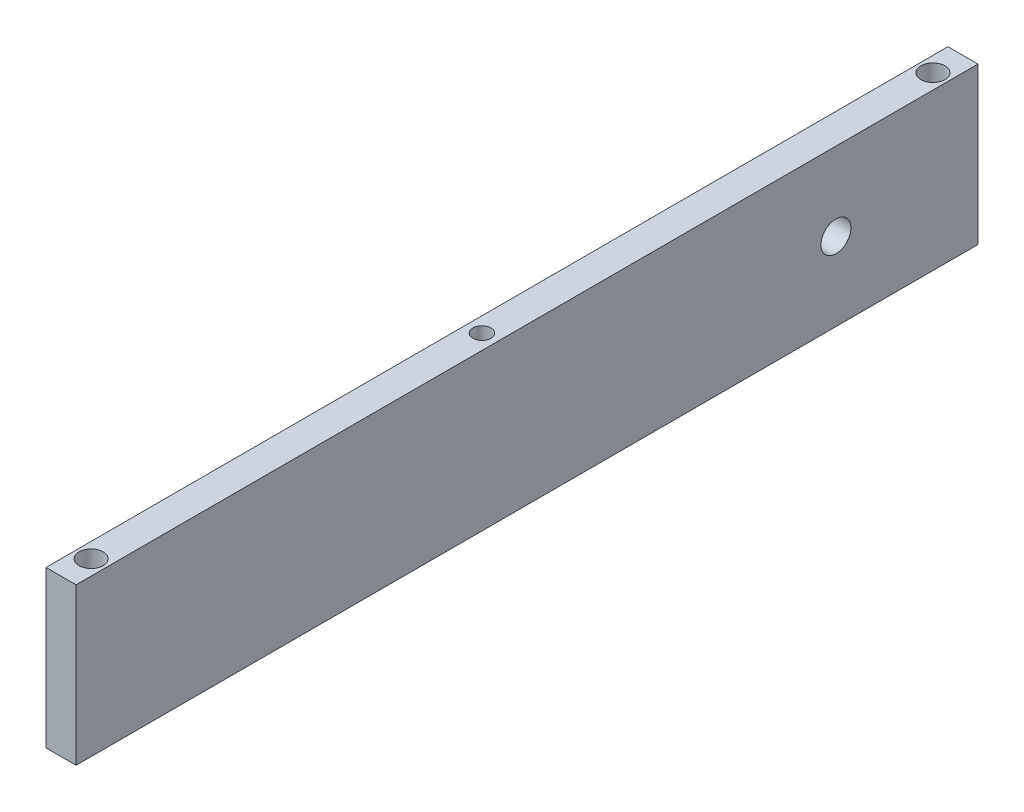
SolidWorks part; units mm, degrees
other "Markup1"
sketch "Sketch6" plane through (0, 0, 0) normal (0.7258, -0.6292, 0.2781) x (-0.261, -0.6259, -0.735)
ref_plane "Front Plane" through (0, 0, 0) normal (0, 0, 1) x (1, 0, 0)
ref_plane "Top Plane" through (0, 0, 0) normal (0, 1, 0) x (1, 0, 0)
ref_plane "Right Plane" through (0, 0, 0) normal (1, 0, 0) x (0, 0, -1)
sketch "Sketch1" plane through (0, 0, 0) normal (0, 0, 1) x (1, 0, 0)
  line L1 (-6.35, 0) -> (-6.35, 33.02)
  line L2 (-6.35, 33.02) -> (0, 33.02)
  line L3 (0, 33.02) -> (0, 0)
  line L6 (-6.35, 0) -> (0, 0)
  dimension "D3" = 6.35
  dimension "D4" = 33.02
extrude "Boss-Extrude1" add sketch "Sketch1" against normal blind 190.5
sketch "Sketch2" plane through (-6.35, 0, 0) normal (-1, 0, 0) x (0, 0, 1)
  line L0 (-190.5, 33.02) -> (-190.5, 0) construction
  circle A1 centre (-160.5, 16.51) radius 3.175
  point P5 (-190.5, 16.51)
  dimension "D1" = 6.35
  dimension "D2" = 30
extrude "Cut-Extrude1" cut sketch "Sketch2" against normal up to next
sketch "Sketch3" plane through (0, 33.02, 0) normal (0, 1, 0) x (1, 0, 0)
  line L0 (-3.175, 190.5) -> (-3.175, 0) construction
  line L1 (0, 190.5) -> (-6.35, 190.5) construction
  line L2 (0, 0) -> (-6.35, 0) construction
  circle A0 centre (-3.175, 6.35) radius 2.54
  circle A1 centre (-3.175, 184.15) radius 2.54
  circle A5 centre (-3.175, 88.9) radius 1.905
  circle A6 centre (-3.175, 88.9) radius 1.905
  dimension "D1" = 5.08
  dimension "D3" = 6.35
  dimension "D2" = 6.35
  dimension "D4" = 0
extrude "Cut-Extrude2" cut sketch "Sketch3" against normal through all
sketch "Sketch4" plane through (0, 0, 0) normal (0, -1, 0) x (1, 0, 0)
  line L0 (-9.525, 0) -> (-9.525, -381) construction
  line L1 (-12.7, 0) -> (0, 0) construction
  line L2 (-12.7, -381) -> (0, -381) construction
  line L3 (0, -381) -> (0, 0) construction
  circle A0 centre (-9.525, -374.65) radius 2.54
  circle A1 centre (-9.525, -6.35) radius 2.54
  dimension "D2" = 5.08
  dimension "D1" = 9.525
  dimension "D3" = 6.35
  dimension "D4" = 6.35
sketch "Sketch5" plane through (0, 0, -190.5) normal (0, 0, -1) x (-1, 0, 0)
  line L1 (6.35, 6.35) -> (0, 6.35)
  line L2 (6.35, 6.35) -> (6.35, 0)
  line L3 (6.35, 0) -> (0, 0)
  line L4 (0, 6.35) -> (0, 0)
